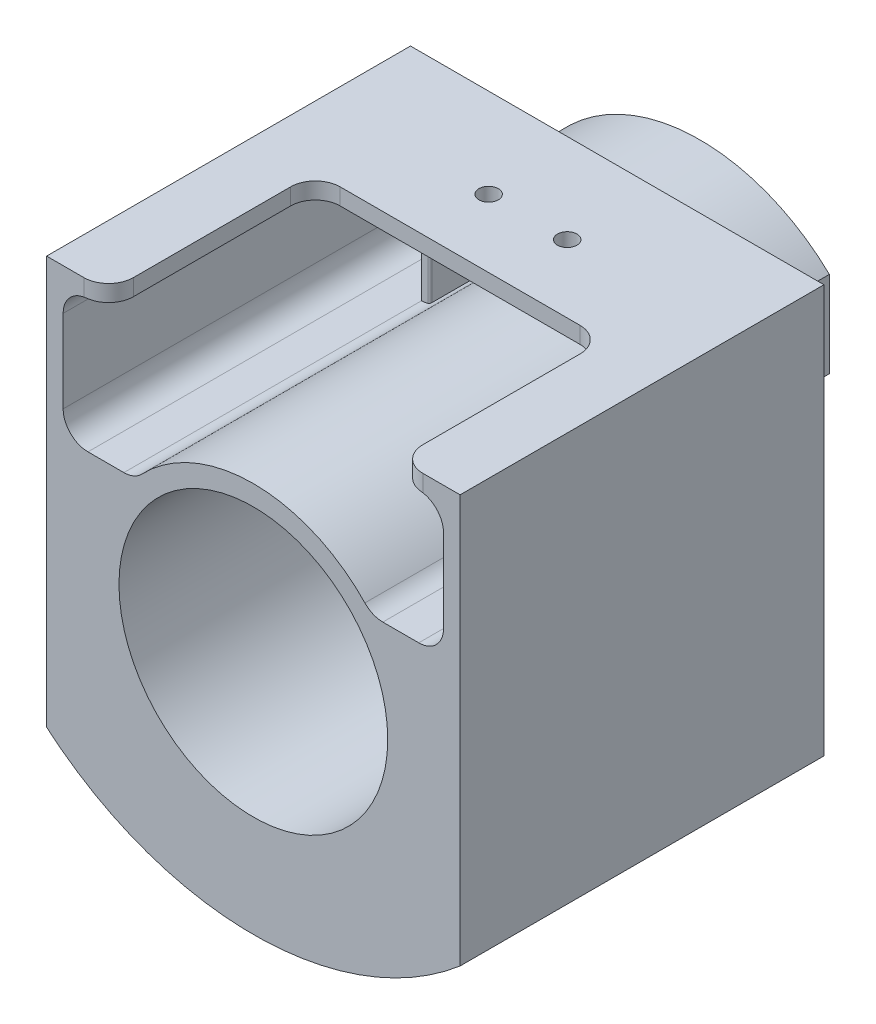
SolidWorks part; units mm, degrees
ref_plane "Front Plane" through (0, 0, 0) normal (0, 0, 1) x (1, 0, 0)
ref_plane "Top Plane" through (0, 0, 0) normal (0, 1, 0) x (1, 0, 0)
ref_plane "Right Plane" through (0, 0, 0) normal (1, 0, 0) x (0, 0, -1)
sketch "Sketch1" plane through (0, 0, 0) normal (0, 0, 1) x (1, 0, 0)
  line L1 (0, 0) -> (0, -38.55) construction
  line L2 (-25, 0) -> (-25, -29.3445)
  line L3 (25, 0) -> (25, -29.3445)
  line L4 (-25, 0) -> (-25, 20)
  line L5 (-25, 20) -> (25, 20)
  line L6 (25, 20) -> (25, 0)
  arc A0 (-25, -29.3445) -> (25, -29.3445) centre (0, 0) ccw
  dimension "D1" = 77.1
  dimension "D2" = 50
  dimension "D3" = 20
extrude "Boss-Extrude2" add sketch "Sketch1" along normal blind 44 from offset 6
sketch "Sketch2" plane through (0, 0, 50) normal (0, 0, 1) x (1, 0, 0)
  line L6 (0, 6.25) -> (0, -26.25) construction
  circle A0 centre (0, -10) radius 16.25
  dimension "D2" = 32.5
  dimension "D1" = 10
extrude "Cut-Extrude1" cut sketch "Sketch2" against normal through all both
sketch "Sketch4" plane through (0, 0, 50) normal (0, 0, 1) x (1, 0, 0)
  line L0 (-23, 18) -> (23, 18)
  line L3 (0, 20) -> (0, 6.25) construction
  line L4 (25, 20) -> (-25, 20) construction
  line L5 (23, 2) -> (14.3178, 2)
  line L6 (-23, 18) -> (-23, 2)
  line L7 (-23, 2) -> (-14.3178, 2)
  line L8 (-25, 20) -> (-25, -29.3445) construction
  line L9 (23, 18) -> (23, 2)
  circle A2 centre (0, -10) radius 16.25 construction
  arc A3 (14.3178, 2) -> (-14.3178, 2) centre (0, -10) ccw
  point P2 (0, 13.125)
  point P14 (0, 18)
  dimension "D1" = 37.3631
  dimension "D2" = 2
  dimension "D3" = 2
  dimension "D4" = 16
extrude "Cut-Extrude3" cut sketch "Sketch4" against normal through all
fillet "Fillet1" radius 3 6 edges at (23, 18, 28) (23, 2, 28) (14.3178, 2, 28) (-14.3178, 2, 28) (-23, 2, 28) (-23, 18, 28)
sketch "Sketch5" plane through (0, 20, 0) normal (0, 1, 0) x (1, 0, 0)
  line L0 (25, -50) -> (-25, -50) construction
  line L1 (-17.5, -50) -> (17.5, -50)
  line L2 (-17.5, -50) -> (-17.5, -25)
  line L3 (-17.5, -25) -> (17.5, -25)
  line L4 (17.5, -50) -> (17.5, -25)
  line L5 (0, 0) -> (0, -50) construction
  dimension "D1" = 35
  dimension "D2" = 25
extrude "Cut-Extrude4" cut sketch "Sketch5" against normal blind 10
fillet "Fillet2" radius 3 4 edges at (17.5, 19, 50) (17.5, 19, 25) (-17.5, 19, 25) (-17.5, 19, 50)
ref_plane "Plane1" through (0, 0, 14) normal (0, 0, 1) x (1, 0, 0)
sketch "Sketch6" plane through (0, 0, 14) normal (0, 0, 1) x (1, 0, 0)
  line L0 (0, -10) -> (0, 3) construction
  line L1 (0, -10) -> (4.4463, 2.216) construction
  circle A1 centre (0, -10) radius 16.25 construction
  circle A3 centre (0, -10) radius 9.5
  circle A8 centre (0, -10) radius 16.25
  circle A9 centre (0, -10) radius 13 construction
  circle A10 centre (4.4463, 2.216) radius 1.65
  circle A11 centre (12.216, -14.4463) radius 1.65
  circle A12 centre (-4.4463, -22.216) radius 1.65
  circle A13 centre (-12.216, -5.5537) radius 1.65
  point P5 (0, 0)
  dimension "D1" = 19
  dimension "D6" = 13
  dimension "D2" = 3.5
  dimension "D3" = 3.3
  dimension "D4" = 20
  dimension "D5" = 4
extrude "Boss-Extrude3" add sketch "Sketch6" against normal blind 5
sketch "Sketch7" plane through (0, 0, 0) normal (1, 0, 0) x (0, 0, -1)
  circle A0 centre (-40.3, -32) radius 2.25
  circle A1 centre (-10.3, -32) radius 2.25
  dimension "D3" = 4.5
  dimension "D1" = 32
  dimension "D2" = 10.3
  dimension "D4" = 30
extrude "Cut-Extrude5" cut sketch "Sketch7" against normal through all both and the other way through all
sketch "Sketch8" plane through (0, 20, 0) normal (0, 1, 0) x (1, 0, 0)
  line L0 (0, -6) -> (0, -25) construction
  line L1 (25, -6) -> (-25, -6) construction
  line L2 (14.5, -25) -> (-14.5, -25) construction
  circle A0 centre (-4.75, -16.8) radius 1.175
  circle A1 centre (4.75, -16.8) radius 1.175
  dimension "D1" = 2.35
  dimension "D2" = 9.5
  dimension "D3" = 10.8
extrude "Cut-Extrude6" cut sketch "Sketch8" against normal up to next contours A0 | A1
sketch "Sketch9" plane through (0, 0, 50) normal (0, 0, 1) x (1, 0, 0)
  line L0 (0, -28.5) -> (0, -5) construction
  line L1 (0, -10) -> (0, -28.5) construction
  line L2 (-15.6553, 2) -> (-15.6553, 11.4123)
  line L3 (15.6553, 2) -> (15.6553, 11.4123)
  line L4 (0, 8.6815) -> (0, 17.6815) construction
  line L5 (-14.6553, 2.1716) -> (-14.6553, 10.5325)
  line L6 (14.6553, 2.1716) -> (14.6553, 10.5325)
  line L7 (-15.6553, 2) -> (-15.6553, 1)
  line L8 (15.6553, 2) -> (15.6553, 1)
  line L9 (14.6553, 2) -> (14.6553, 10.9784) construction
  line L10 (-14.6553, 2) -> (-14.6553, 10.9784) construction
  arc A0 (13.4892, 2.9245) -> (-13.4892, 2.9245) centre (0, -10) ccw construction
  arc A1 (13.4892, 2.9245) -> (-13.4892, 2.9245) centre (0, -10) ccw
  arc A3 (-15.6553, 11.4123) -> (15.6553, 11.4123) centre (0, -5) cw
  arc A4 (13.4892, 2.9245) -> (15.6553, 2) centre (15.6553, 5) ccw construction
  arc A5 (-15.6553, 2) -> (-13.4892, 2.9245) centre (-15.6553, 5) ccw construction
  arc A6 (13.4892, 2.9245) -> (15.6553, 2) centre (15.6553, 5) ccw
  arc A7 (-15.6553, 2) -> (-13.4892, 2.9245) centre (-15.6553, 5) ccw
  arc A8 (12.7671, 2.2327) -> (15.6553, 1) centre (15.6553, 5) ccw
  arc A9 (12.7671, 2.2327) -> (-12.7671, 2.2327) centre (0, -10) ccw
  arc A10 (-15.6553, 1) -> (-12.7671, 2.2327) centre (-15.6553, 5) ccw
  arc A11 (-14.3156, 11.2835) -> (14.3156, 11.2835) centre (0, -5) cw
  arc A12 (-14.6553, 10.9784) -> (14.6553, 10.9784) centre (0, -5) cw construction
  arc A13 (14.6553, 10.5325) -> (14.3156, 11.2835) centre (13.6553, 10.5325) ccw
  arc A14 (-14.6553, 10.5325) -> (-14.3156, 11.2835) centre (-13.6553, 10.5325) cw
  dimension "D1" = 9
  dimension "D2" = 1
  dimension "D4" = 1
  dimension "Ring Gear Outer Dia to Center" = 23.5
  dimension "Pinion to Ring Gear Outer Diameter" = 18.5
  dimension "D3" = 1
extrude "Boss-Extrude4" add sketch "Sketch9" along normal blind 8 and the other way blind 10 from surface contours L5 A11 L6 L2 L3 A3 A6 | L7 A10 A9 A8 L8 L2 L3 A6 region at (-15.0935, 1.7255, 50) region at (-15.3051, 6.7061, 50) starting at face at (0, 7.9303, 6)
fillet "Fillet5" radius 0.25 8 edges at (14.0281, 2.4797, -4) (-14.0281, 2.4797, -4) (14.6553, 6.352, -4) (14.5664, 10.9446, -4) (-14.6553, 6.352, -4) (-14.5664, 10.9446, -4) (0, 8.6815, -4) (0, 16.6815, -4)
fillet "Fillet6" radius 0.25 5 edges at (14.6553, 6.352, 14) (14.5664, 10.9446, 14) (-14.6553, 6.352, 14) (-14.5664, 10.9446, 14) (0, 16.6815, 14)
